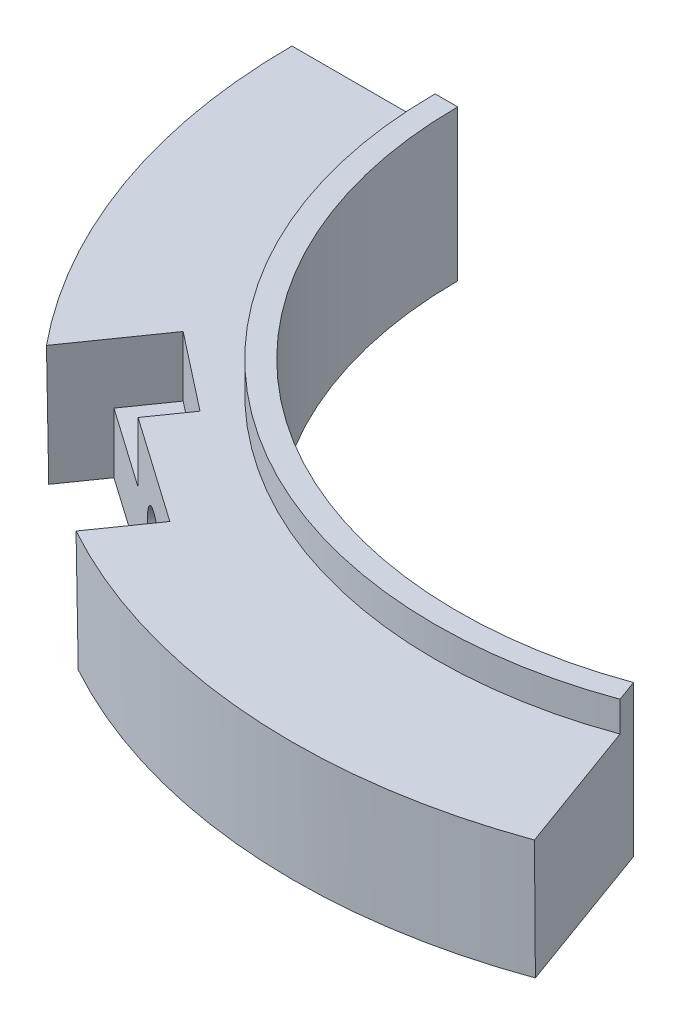
SolidWorks part; units mm, degrees
ref_plane "Front Plane" through (0, 0, 0) normal (0, 0, 1) x (1, 0, 0)
ref_plane "Top Plane" through (0, 0, 0) normal (0, 1, 0) x (1, 0, 0)
ref_plane "Right Plane" through (0, 0, 0) normal (1, 0, 0) x (0, 0, -1)
sketch "Sketch1" plane through (0, 0, 0) normal (0, 0, 1) x (1, 0, 0)
  line L0 (0, 0) -> (0, 8) construction
  line L2 (-29, 0) -> (-29, 8)
  line L3 (-29, 8) -> (-40, 8)
  line L4 (-40, 8) -> (-39.8964, 0.0007)
  line L5 (-39.8964, 0.0007) -> (-29, 0)
revolve "Revolve1" add sketch "Sketch1" angle 110 about L0
sketch "Sketch2" plane through (0, 8, 0) normal (0, 1, 0) x (1, 0, 0)
  line L0 (9.9186, -27.2511) -> (13.6808, -37.5877) construction
  line L1 (-29, 0) -> (-40, 0) construction
  line L4 (-29, 0) -> (-40, 0)
  line L5 (13.6808, -37.5877) -> (9.9186, -27.2511)
  line L6 (-29, 0) -> (-30.5, 0)
  line L7 (10.4316, -28.6606) -> (9.9186, -27.2511)
  arc A1 (10.4316, -28.6606) -> (-30.5, 0) centre (0, 0) cw
  arc A4 (-29, 0) -> (9.9186, -27.2511) centre (0, 0) ccw
  arc A5 (-40, 0) -> (13.6808, -37.5877) centre (0, 0) ccw
  arc A6 (-29, 0) -> (9.9186, -27.2511) centre (0, 0) ccw
  dimension "D1" = 0
extrude "Boss-Extrude2" add sketch "Sketch2" along normal blind 2 contours A1 L6 A6 L7
ref_plane "Plane1" through (0, 0, 0) normal (0.8192, 0, 0.5736) x (0.5736, 0, -0.8192)
sketch "Sketch6" plane through (0, 0, 0) normal (0.8192, 0, 0.5736) x (0.5736, 0, -0.8192)
  line L0 (-40, 8) -> (-39.8964, 0.0007) construction
  line L1 (-40.2779, 29.46) -> (-35.2989, 29.46)
  line L2 (-40.2779, 29.46) -> (-40.2779, -5.6879)
  line L3 (-40.2779, -5.6879) -> (-35.2989, -5.6879)
  line L4 (-35.2989, 29.46) -> (-35.2989, -5.6879)
extrude "Cut-Extrude3" cut sketch "Sketch6" against normal blind 4.3 and the other way blind 4.3
sketch "Sketch8" plane through (-20.2466, 0, 28.9152) normal (-0.5736, 0, 0.8192) x (0.8192, 0, 0.5736)
  circle A0 centre (0, 3.8735) radius 1.6
hole_wizard "CSK for M3 Countersunk Flat Head Screw1" positions "3DSketch2" profile "Sketch12" countersink size "M3" standard "DIN" end condition through all
sketch3d "3DSketch2"
  point P0 (-16.6932, 3.7995, 23.7136)
sketch "Sketch12" plane through (-16.6932, 3.7995, 23.7136) normal (0, 1, 0) x (-0.8177, 0, -0.5756)
  line L0 (0, 0) -> (0, 26.7336)
  line L1 (0, 26.7336) -> (1.7, 26.7336)
  line L2 (1.7, 26.7336) -> (1.7, 1.45)
  line L3 (1.7, 1.45) -> (3.15, 0)
  line L5 (3.15, 0) -> (0, 0)
  line L6 (-1.7, 1.45) -> (-3.15, 0) construction
  line L11 (0, -6.35) -> (0, 107.95) construction
  dimension "Thru Hole Dia." = 3.4
  dimension "Thru Hole Depth" = 26.7336
  dimension "Near C'Sink Dia." = 6.3
  dimension "Near C'Sink Angle" = 90
sketch "Sketch13" plane through (0, 8, 0) normal (0, 1, 0) x (1, 0, 0)
  line L0 (-23.769, -26.4488) -> (-29.0935, -22.7206)
  line L1 (-29.0935, -22.7206) -> (-32.3447, -27.3638)
  line L2 (-32.3447, -27.3638) -> (-27.0202, -31.092)
  line L3 (-27.0202, -31.092) -> (-23.769, -26.4488)
extrude "Cut-Extrude4" cut sketch "Sketch13" against normal through all
sketch "Sketch14" plane through (0, 8, 0) normal (0, 1, 0) x (1, 0, 0)
  line L0 (-29.0935, -22.7206) -> (-23.7562, -26.4578)
  line L1 (-16.7243, -31.3816) -> (-29.0935, -22.7206) construction
  line L2 (-23.7562, -26.4578) -> (-22.0629, -24.0394)
  line L3 (-22.0629, -24.0394) -> (-27.2022, -20.0196)
  line L4 (-27.2022, -20.0196) -> (-29.0935, -22.7206)
  point P5 (-22.0629, -24.0394)
  point P8 (0, 0)
  point P9 (0, 0)
extrude "Cut-Extrude5" cut sketch "Sketch14" against normal blind 4
